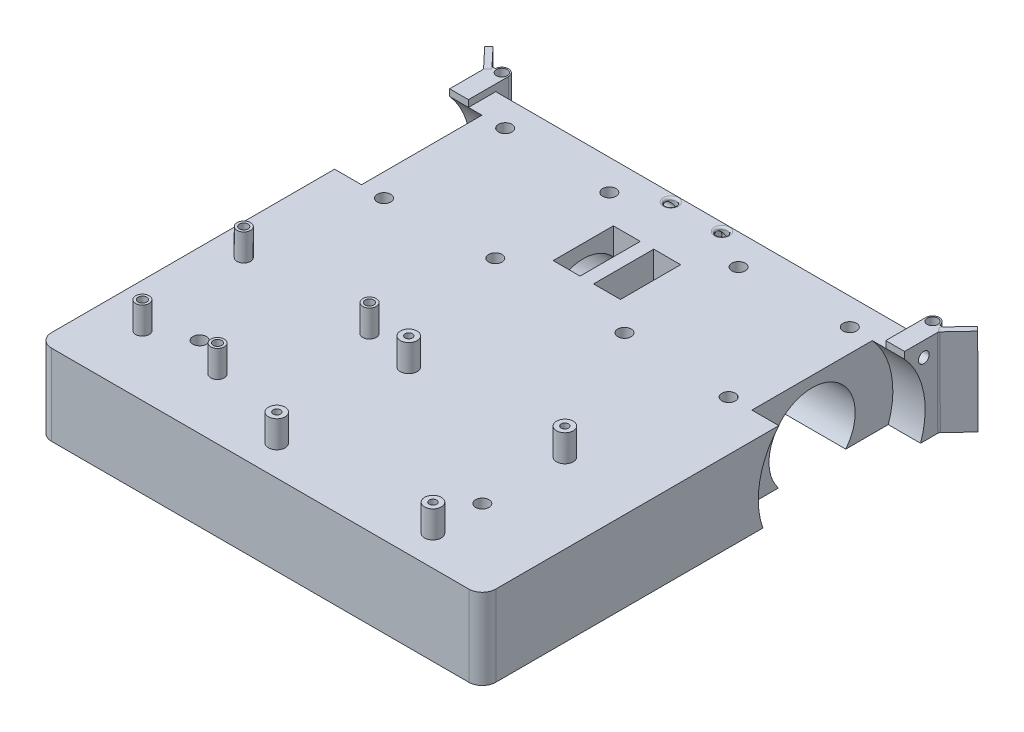
SolidWorks part; units mm, degrees
ref_plane "Plan de face" through (0, 0, 0) normal (0, 0, 1) x (1, 0, 0)
ref_plane "Plan de dessus" through (0, 0, 0) normal (0, 1, 0) x (1, 0, 0)
ref_plane "Plan de droite" through (0, 0, 0) normal (1, 0, 0) x (0, 0, -1)
sketch "Esquisse2" plane through (0, 0, 0) normal (0, 1, 0) x (1, 0, 0)
  line L1 (82.5, 82.5) -> (-82.5, 82.5)
  line L2 (82.5, 82.5) -> (82.5, -82.5)
  line L3 (82.5, -82.5) -> (-82.5, -82.5)
  line L4 (-82.5, 82.5) -> (-82.5, -82.5)
  line L5 (82.5, 82.5) -> (-82.5, -82.5) construction
  line L6 (82.5, -82.5) -> (-82.5, 82.5) construction
  point P0 (0, 0)
  dimension "D1" = 165
  dimension "D2" = 165
extrude "BASE" add sketch "Esquisse2" along normal blind 30
sketch "Esquisse3" plane through (82.5, 0, 0) normal (1, 0, 0) x (0, 0, -1)
  line L0 (82.5, 10) -> (31.0775, 10) construction
  line L1 (82.5, 30) -> (82.5, 0) construction
  line L2 (-82.5, 0) -> (82.5, 0) construction
  circle A0 centre (50, 10) radius 15
  point P4 (50, 10)
  dimension "D3" = 30
  dimension "D1" = 32.5
  dimension "D2" = 10
extrude "BLOC MOTEUR 1." cut sketch "Esquisse3" against normal blind 80
sketch "Esquisse4" plane through (0, 0, 0) normal (0, -1, 0) x (1, 0, 0)
  line L0 (2.5, -61.1803) -> (82.5, -61.1803) construction
  line L1 (2.5, -38.8197) -> (12.5, -38.8197)
  line L2 (2.5, -38.8197) -> (2.5, -61.1803)
  line L3 (2.5, -61.1803) -> (12.5, -61.1803)
  line L4 (12.5, -38.8197) -> (12.5, -61.1803)
  dimension "D1" = 10
extrude "ACCES MOTEUR" cut sketch "Esquisse4" against normal blind 37
ref_plane "PLAN SYM " through (0, 0, 0) normal (1, 0, 0) x (0, 0, -1)
sketch "Esquisse6" plane through (82.5, 0, 0) normal (1, 0, 0) x (0, 0, -1)
  line L0 (35, 10) -> (65, 10) construction
  arc A0 (38.8197, 20) -> (38.8197, 0) centre (50, 10) ccw construction
  arc A1 (61.1803, 0) -> (38.8197, 0) centre (50, 10) ccw construction
  circle A2 centre (50, 10) radius 16.01
  dimension "D1" = 32.02
extrude "BLOC MOTEUR 2" cut sketch "Esquisse6" against normal blind 37
mirror "SYM BLOC MOTEUR" about plane through (0, 0, 0) normal (1, 0, 0) of "ACCES MOTEUR", "BLOC MOTEUR 1.", "BLOC MOTEUR 2"
sketch "Esquisse7" plane through (0, 0, 0) normal (0, -1, 0) x (1, 0, 0)
  line L0 (-64, -37.4972) -> (-64, -72.5028) construction
  line L1 (-82.5, -37.4972) -> (-45.5, -37.4972) construction
  line L2 (-24, -38.8197) -> (-24, -67.469) construction
  line L3 (-45.5, -38.8197) -> (-2.5, -38.8197) construction
  line L4 (-45.5, -62.5028) -> (-82.5, -62.5028) construction
  line L5 (-2.5, -61.1803) -> (-45.5, -61.1803) construction
  line L6 (-64, -37.4972) -> (-64, -13.9891) construction
  line L7 (-24, -71.1803) -> (-24, -20.9291) construction
  circle A0 centre (-64, -27.4972) radius 2.5
  circle A1 centre (-24, -28.8197) radius 2.5
  circle A2 centre (-24, -71.1803) radius 2.5
  circle A3 centre (-64, -72.5028) radius 2.5
  point P8 (-64, -27.4972)
  point P9 (-64, -72.5028)
  point P10 (-24, -71.1803)
  point P11 (-24, -28.8197)
  dimension "D5" = 5
  dimension "D6" = 5
  dimension "D7" = 5
  dimension "D8" = 5
  dimension "D1" = 10
  dimension "D2" = 10
  dimension "D3" = 10
  dimension "D4" = 10
extrude "VIS MOTEUR" cut sketch "Esquisse7" against normal through all
mirror "SYM VIS" about plane through (0, 0, 0) normal (1, 0, 0) of "VIS MOTEUR"
sketch "Esquisse8" plane through (0, 0, 0) normal (0, -1, 0) x (1, 0, 0)
  line L0 (-82.5, 82.5) -> (82.5, 82.5) construction
  line L1 (-82.5, -37.4972) -> (-82.5, 82.5) construction
  line L2 (82.5, 82.5) -> (82.5, -37.4972) construction
  circle A0 centre (-52.5, 52.5) radius 2.5
  circle A1 centre (52.5, 52.5) radius 2.5
  point P0 (-52.5, 52.5)
  point P1 (52.5, 52.5)
  dimension "D5" = 5
  dimension "D6" = 5
  dimension "D1" = 30
  dimension "D2" = 30
  dimension "D3" = 30
  dimension "D4" = 30
extrude "VIS PATIN" cut sketch "Esquisse8" against normal through all
sketch "Esquisse9" plane through (0, 30, 0) normal (0, 1, 0) x (1, 0, 0)
  line L0 (-5.1247, -22.1943) -> (52.8753, -22.1943) construction
  line L1 (-5.1247, -71.1943) -> (52.8753, -71.1943) construction
  line L2 (52.8753, -22.1943) -> (52.8753, -70.2718) construction
  circle A0 centre (-5.1247, -22.1943) radius 1.375
  circle A1 centre (52.8753, -22.1943) radius 1.375
  circle A2 centre (52.8753, -71.1943) radius 1.375
  circle A3 centre (-5.1247, -71.1943) radius 1.375
  circle A4 centre (-5.1247, -22.1943) radius 3.1
  circle A5 centre (52.8753, -22.1943) radius 3.1
  circle A6 centre (-5.1247, -71.1943) radius 3.1
  circle A7 centre (52.8753, -71.1943) radius 3.1
  dimension "D1" = 2.75
  dimension "D2" = 2.75
  dimension "D3" = 2.75
  dimension "D4" = 2.75
  dimension "D9" = 6.2
  dimension "D10" = 6.2
  dimension "D11" = 6.2
  dimension "D12" = 6.2
  dimension "D5" = 58
  dimension "D6" = 58
  dimension "D7" = 49
extrude "SUPPORT RASP" add sketch "Esquisse9" along normal blind 10
sketch "Esquisse11" plane through (0, 30, 0) normal (0, 1, 0) x (1, 0, 0)
  circle A0 centre (-70.9338, -17.6706) radius 1.6
  circle A1 centre (-70.9338, -17.6706) radius 2.5
  circle A2 centre (-23.1238, -18.7706) radius 1.6
  circle A3 centre (-23.1238, -18.7706) radius 2.5
  circle A4 centre (-66.2338, -60.0106) radius 1.6
  circle A5 centre (-66.2338, -60.0106) radius 2.5
  circle A6 centre (-38.3338, -60.0106) radius 1.6
  circle A7 centre (-38.3338, -60.0106) radius 2.5
  point P0 (-66.2338, -60.0106)
  point P1 (-38.3338, -60.0106)
  point P2 (-23.1238, -18.7706)
  point P3 (-70.9338, -17.6706)
  dimension "D8" = 3.2
  dimension "D9" = 5
  dimension "D10" = 3.2
  dimension "D11" = 5
  dimension "D12" = 3.2
  dimension "D13" = 3.2
  dimension "D14" = 5
  dimension "D15" = 5
  dimension "D1" = 4.7
  dimension "D2" = 47.81
  dimension "D3" = 15.21
  dimension "D4" = 27.9
  dimension "D5" = 41.24
  dimension "D6" = 42.34
  dimension "D7" = 0
extrude "SUPPORT ARDUINO" add sketch "Esquisse11" along normal blind 10
fillet "CONGE EXT" radius 5 2 edges at (82.5, 15, 82.5) (-82.5, 15, 82.5)
sketch "Esquisse12" plane through (-82.5, 0, 0) normal (-1, 0, 0) x (0, 0, 1)
  circle A0 centre (-50, 10) radius 30
  dimension "D1" = 60
extrude "ESPACE ROUE " cut sketch "Esquisse12" against normal blind 10
mirror "SYM ESPACE ROUE" about plane through (0, 0, 0) normal (1, 0, 0) of "ESPACE ROUE "
sketch "Esquisse14" plane through (0, 30, 0) normal (0, 1, 0) x (1, 0, 0)
  line L0 (-82.5, 82.5) -> (82.5, 82.5) construction
  line L1 (-80, 79.7079) -> (-80, 91.2393) construction
  line L2 (-82.5, 87.2451) -> (-82.5, 82.5)
  line L3 (-77.5, 87.2451) -> (-77.5, 82.5)
  line L4 (1.7488, 70.1549) -> (0, 73.4609) construction
  line L5 (0, 73.4609) -> (0, 103.9135) construction
  line L6 (77.5, 87.2451) -> (77.5, 82.5)
  line L7 (82.5, 87.2451) -> (82.5, 82.5)
  arc A0 (-77.5, 87.2451) -> (-82.5, 87.2451) centre (-80, 87.2451) ccw
  circle A1 centre (-80, 87.2451) radius 2
  circle A2 centre (80, 87.2451) radius 2
  arc A3 (77.5, 87.2451) -> (82.5, 87.2451) centre (80, 87.2451) cw
  point P4 (-80, 82.5)
  point P5 (0, 82.5)
  line M29 (82.5, 82.5) -> (-82.5, 82.5)
  dimension "D3" = 4
  dimension "D1" = 165
  dimension "D2" = 80
extrude "FIXE PORTE 1" add sketch "Esquisse14" against normal blind 10 and the other way blind 2.5 contours L3 A0 L2 A1 M29 | A3 L6 L7 A2 M29 region at (-80, 30, -85.0582) region at (80, 30, -85.0582)
sketch "Esquisse15" plane through (0, 30, 0) normal (0, 1, 0) x (1, 0, 0)
  line L0 (82.5, 72.3607) -> (72.5, 72.3607) construction
  line L1 (-77.5, 82.5) -> (-82.5, 82.5)
  line L2 (-77.5, 82.5) -> (-77.5, 72.3607)
  line L3 (-77.5, 72.3607) -> (-82.5, 72.3607)
  line L4 (-82.5, 82.5) -> (-82.5, 72.3607)
  line L5 (82.5, 82.5) -> (77.5, 82.5)
  line L6 (82.5, 82.5) -> (82.5, 72.3607)
  line L7 (82.5, 72.3607) -> (77.5, 72.3607)
  line L8 (77.5, 82.5) -> (77.5, 72.3607)
extrude "FIXE PORTE 2" add sketch "Esquisse15" along normal blind 2.5
sketch "Esquisse16" plane through (0, 0, 0) normal (0, -1, 0) x (1, 0, 0)
  line L0 (-82.5, -87.2451) -> (-82.5, -82.5)
  line L1 (-82.5, -82.5) -> (-77.5, -82.5)
  line L2 (82.5, -82.5) -> (-82.5, -82.5) construction
  line L3 (-77.5, -82.5) -> (-82.5, -82.5) construction
  line L4 (-77.5, -82.5) -> (-77.5, -87.2451)
  line L5 (0, -73.149) -> (0, -105.1692) construction
  line L6 (82.5, -87.2451) -> (82.5, -82.5)
  line L7 (77.5, -82.5) -> (77.5, -87.2451)
  circle A0 centre (-80, -87.2451) radius 2
  arc A1 (-82.5, -87.2451) -> (-77.5, -87.2451) centre (-80, -87.2451) ccw
  arc A2 (82.5, -87.2451) -> (77.5, -87.2451) centre (80, -87.2451) cw
  circle A3 centre (80, -87.2451) radius 2
  line M40 (-82.5, -82.5) -> (82.5, -82.5)
extrude "FIXE PORTE 3" add sketch "Esquisse16" against normal blind 10 contours L0 A1 L4 A0 M40 | A2 L6 L7 A3 M40 region at (80, 0, -85.0582) region at (-80, 0, -85.0582)
sketch "Esquisse18" plane through (82.5, 0, 0) normal (1, 0, 0) x (0, 0, -1)
  line L0 (82.5, 30) -> (72.3607, 30) construction
  line L1 (82.5, 20) -> (82.5, 30) construction
  circle A0 centre (79.5, 27) radius 2
  dimension "D1" = 4
  dimension "D2" = 3
  dimension "D3" = 3
extrude "VIDE CORDE COTE" cut sketch "Esquisse18" against normal blind 75
sketch "Esquisse19" plane through (0, 30, 0) normal (0, 1, 0) x (1, 0, 0)
  line L0 (0, 82.5) -> (0, 66.3305) construction
  line L1 (77.5, 82.5) -> (-77.5, 82.5) construction
  line L2 (82.5, 79.5) -> (9.5, 79.5) construction
  line L3 (82.5, 87.2451) -> (82.5, 72.3607) construction
  circle A0 centre (9.5, 79.5) radius 2
  dimension "D3" = 4
  dimension "D1" = 3
  dimension "D2" = 73
extrude "VIDEO CORDE HAUT" cut sketch "Esquisse19" against normal blind 5
mirror "SYM CORDE" about plane through (0, 0, 0) normal (1, 0, 0) of "VIDEO CORDE HAUT", "VIDE CORDE COTE"
fillet "CONGE CORDE" radius 0.8 2 edges at (-9.5, 30, -77.5) (9.5, 30, -77.5)
sketch "Esquisse20" plane through (82.5, 0, 0) normal (1, 0, 0) x (0, 0, -1)
  line L0 (72.3607, 30) -> (72.3607, 32.5)
  line L1 (72.3607, 32.5) -> (87.3607, 32.5)
  line L2 (87.3607, 32.5) -> (87.3607, 0)
  line L3 (87.3607, 0) -> (78.2843, 0)
  circle A0 centre (79.5, 27) radius 2
  arc A1 (78.2843, 0) -> (72.3607, 30) centre (50, 10) ccw
  dimension "D1" = 15
extrude "BOSS MAX PORTE" add sketch "Esquisse20" along normal blind 2
mirror "SYM MAX PORTE" about plane through (0, 0, 0) normal (1, 0, 0) of "BOSS MAX PORTE"
ref_point "POINT CONST PORTE 45" parameters "D1"=2
ref_plane "PLAN PORTE 45" through (82.4008, 0.3109, -87.453) normal (0.6858, 0.0026, -0.7278) x (-0.7278, 0.0024, -0.6858)
sketch "Esquisse21" plane through (0, 0, -87.3607) normal (0, 0, -1) x (-1, 0, 0)
  line L0 (-84.5, 32.5) -> (-84.5, 0) construction
sketch "Esquisse22" plane through (82.4008, 0.3109, -87.453) normal (0.6858, 0.0026, -0.7278) x (-0.7278, 0.0024, -0.6858)
  line L0 (-1.5919, -0.3106) -> (-0.9698, -0.3106)
  line L1 (-0.9698, -0.3106) -> (-0.9698, 32.1917)
  line L2 (-0.9698, 32.1917) -> (-3.1596, 32.1978)
  line L3 (-1.5127, 32.1892) -> (-11.7991, 32.2425) construction
  line L4 (-3.1596, 32.1978) -> (-3.1596, -0.3024)
  line L5 (-7.8162, -0.2783) -> (-1.5919, -0.3106) construction
  line L6 (-3.1596, -0.3024) -> (-1.5919, -0.3106)
extrude "BOSS PORTE 45" add sketch "Esquisse22" along normal blind 10 and the other way blind 0.5
mirror "SYM MAX PORTE 45" about plane through (0, 0, 0) normal (1, 0, 0) of "BOSS PORTE 45"
fillet "CONGE PORTE 45" radius 1 2 edges at (84.5, 16.25, -85.0169) (-84.5, 16.25, -85.0169)
